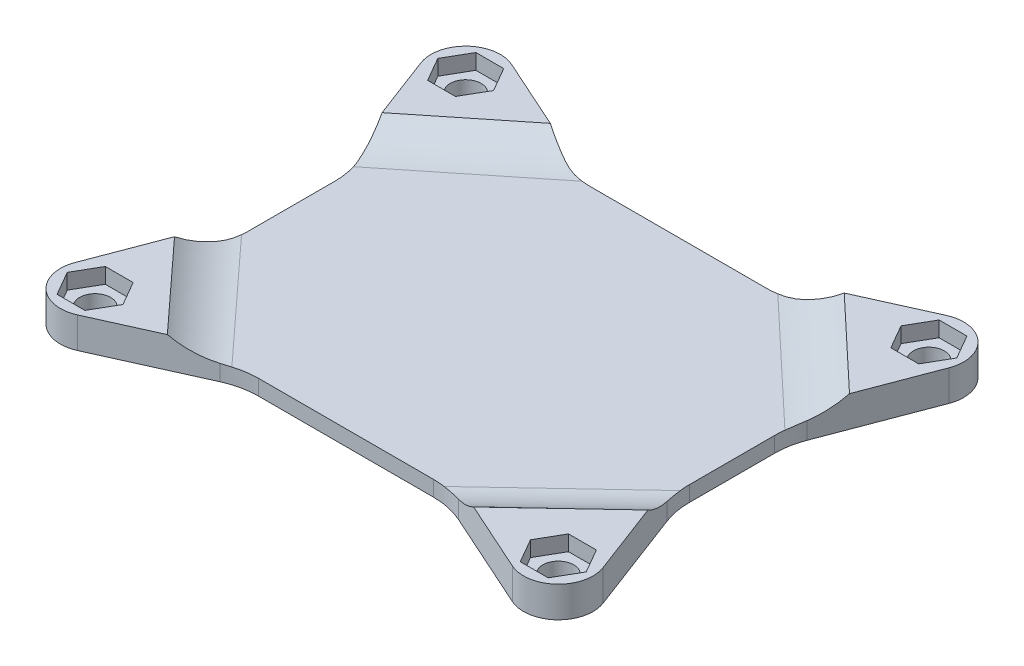
SolidWorks part; units mm, degrees
ref_plane "Front Plane" through (0, 0, 0) normal (0, 0, 1) x (1, 0, 0)
ref_plane "Top Plane" through (0, 0, 0) normal (0, 1, 0) x (1, 0, 0)
ref_plane "Right Plane" through (0, 0, 0) normal (1, 0, 0) x (0, 0, -1)
sketch "Sketch1" plane through (0, 0, 0) normal (0, 1, 0) x (1, 0, 0)
  line L0 (-28.1534, 28.1037) -> (-13.4782, 21.5)
  line L1 (-30, -24) -> (30, -24) construction
  line L2 (-30, -24) -> (-30, 24) construction
  line L3 (-30, 24) -> (30, 24) construction
  line L4 (30, -24) -> (30, 24) construction
  line L5 (-30, -24) -> (30, 24) construction
  line L6 (-30, 24) -> (30, -24) construction
  line L7 (-13.4782, 21.5) -> (13.4782, 21.5)
  line L8 (13.4782, 21.5) -> (28.1534, 28.1037)
  line L9 (-34.2075, 22.404) -> (-28.5, 7.3575)
  line L10 (-28.5, 7.3575) -> (-28.5, -7.3575)
  line L11 (-28.5, -7.3575) -> (-34.2075, -22.404)
  line L12 (-28.1534, -28.1037) -> (-13.4782, -21.5)
  line L13 (-13.4782, -21.5) -> (13.4782, -21.5)
  line L14 (13.4782, -21.5) -> (28.1534, -28.1037)
  line L15 (34.2075, -22.404) -> (28.5, -7.3575)
  line L16 (28.5, -7.3575) -> (28.5, 7.3575)
  line L17 (28.5, 7.3575) -> (34.2075, 22.404)
  line L18 (-28.5, 0) -> (-30, 0) construction
  line L19 (28.5, 0) -> (30, 0) construction
  line L20 (0, 21.5) -> (0, 24) construction
  line L21 (0, -21.5) -> (0, -24) construction
  circle A0 centre (-30, 24) radius 4.5
  circle A1 centre (-30, 24) radius 2
  circle A2 centre (30, 24) radius 4.5
  circle A3 centre (30, 24) radius 2
  circle A4 centre (30, -24) radius 4.5
  circle A5 centre (30, -24) radius 2
  circle A6 centre (-30, -24) radius 4.5
  circle A7 centre (-30, -24) radius 2
  point P0 (0, 0)
  dimension "D1" = 4
  dimension "D2" = 2.5
  dimension "D3" = 60
  dimension "D4" = 48
  dimension "D5" = 57
  dimension "D6" = 43
  dimension "D7" = 45
  dimension "D8" = 45
  dimension "D9" = 45
extrude "Boss-Extrude1" add sketch "Sketch1" along normal blind 2 contours A6 L12 L13 L14 A4 L15 L16 L17 A2 L8 L7 L0 A0 L9 L10 L11 | A6 A7 | A4 A5 | A2 A3 | A0 A1 region at (0, 0, 0) region at (-26.328, 0, -26.3743) region at (32.3743, 0, -27.672) region at (-29.2117, 0, 19.6989) region at (34.3011, 0, 23.2117)
sketch "Sketch2" plane through (0, 2, 0) normal (0, 1, 0) x (1, 0, 0)
  line L0 (28.1534, -28.1037) -> (19.0341, -24.0001)
  line L1 (26.3916, -24) -> (28.1958, -27.125)
  line L2 (28.1958, -27.125) -> (31.8042, -27.125)
  line L3 (31.8042, -27.125) -> (33.6084, -24)
  line L4 (33.6084, -24) -> (31.8042, -20.875)
  line L5 (31.8042, -20.875) -> (28.1958, -20.875)
  line L6 (28.1958, -20.875) -> (26.3916, -24)
  line L7 (-26.3916, -24) -> (-28.1958, -20.875)
  line L8 (-28.1958, -20.875) -> (-31.8042, -20.875)
  line L9 (-31.8042, -20.875) -> (-33.6084, -24)
  line L10 (-33.6084, -24) -> (-31.8042, -27.125)
  line L11 (-31.8042, -27.125) -> (-28.1958, -27.125)
  line L12 (-28.1958, -27.125) -> (-26.3916, -24)
  line L13 (26.3916, 24) -> (28.1958, 20.875)
  line L14 (28.1958, 20.875) -> (31.8042, 20.875)
  line L15 (31.8042, 20.875) -> (33.6084, 24)
  line L16 (33.6084, 24) -> (31.8042, 27.125)
  line L17 (31.8042, 27.125) -> (28.1958, 27.125)
  line L18 (28.1958, 27.125) -> (26.3916, 24)
  line L19 (-26.3916, 24) -> (-28.1958, 27.125)
  line L20 (-28.1958, 27.125) -> (-31.8042, 27.125)
  line L21 (-31.8042, 27.125) -> (-33.6084, 24)
  line L22 (-33.6084, 24) -> (-31.8042, 20.875)
  line L23 (-31.8042, 20.875) -> (-28.1958, 20.875)
  line L24 (-28.1958, 20.875) -> (-26.3916, 24)
  line L25 (13.4782, -21.5) -> (28.1534, -28.1037) construction
  line L26 (19.0341, -24.0001) -> (30.6608, -13.0541)
  line L27 (34.2075, -22.404) -> (28.5, -7.3575) construction
  line L28 (30.6608, -13.0541) -> (34.2075, -22.404)
  line L29 (-30.6608, -13.0541) -> (-20.1426, -24.4989)
  line L30 (-28.5, -7.3575) -> (-34.2075, -22.404) construction
  line L31 (-28.1534, -28.1037) -> (-13.4782, -21.5) construction
  line L32 (-20.1426, -24.4989) -> (-28.1534, -28.1037)
  line L33 (-34.2075, -22.404) -> (-30.6608, -13.0541)
  line L34 (-19.0341, 24.0001) -> (-31.1352, 14.3045)
  line L35 (-28.1534, 28.1037) -> (-13.4782, 21.5) construction
  line L36 (-34.2075, 22.404) -> (-28.5, 7.3575) construction
  line L37 (-31.1352, 14.3045) -> (-34.2075, 22.404)
  line L38 (-28.1534, 28.1037) -> (-19.0341, 24.0001)
  line L39 (30.6608, 13.0541) -> (19.0339, 24)
  line L40 (28.5, 7.3575) -> (34.2075, 22.404) construction
  line L41 (13.4782, 21.5) -> (28.1534, 28.1037) construction
  line L42 (19.0339, 24) -> (28.1534, 28.1037)
  line L43 (34.2075, 22.404) -> (30.6608, 13.0541)
  circle A0 centre (30, -24) radius 3.125 construction
  circle A1 centre (-30, -24) radius 3.125 construction
  circle A2 centre (30, 24) radius 3.125 construction
  circle A3 centre (-30, 24) radius 3.125 construction
  arc A4 (28.1534, -28.1037) -> (34.2075, -22.404) centre (30, -24) ccw
  arc A5 (28.1534, -28.1037) -> (34.2075, -22.404) centre (30, -24) ccw construction
  arc A6 (-28.1534, -28.1037) -> (-34.2075, -22.404) centre (-30, -24) cw
  arc A7 (-34.2075, 22.404) -> (-28.1534, 28.1037) centre (-30, 24) cw
  arc A8 (28.1534, 28.1037) -> (34.2075, 22.404) centre (30, 24) cw
  dimension "D1" = 6.25
  dimension "D2" = 10
extrude "Boss-Extrude2" add sketch "Sketch2" along normal blind 2
fillet "Fillet1" radius 10 8 edges at (-28.5, 1, 7.3575) (-28.5, 1, -7.3575) (-13.4782, 1, -21.5) (13.4782, 1, -21.5) (28.5, 1, -7.3575) (28.5, 1, 7.3575) (13.4782, 1, 21.5) (-13.4782, 1, 21.5)
fillet "Fillet3" radius 10 4 edges at (-25.0847, 2, -19.1523) (-25.4017, 2, 18.7765) (24.8473, 2, -18.527)
